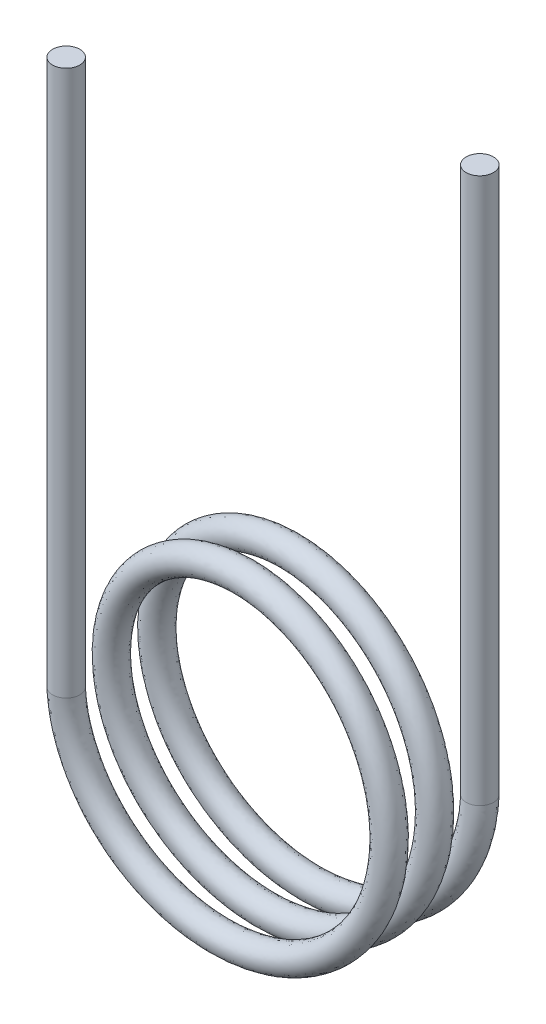
SolidWorks part; units mm, degrees
note: The reader was unsure of these and kept them because the rebuilt part matched: shared geometry of "Esboço2<2>".
ref_plane "Plano frontal" through (0, 0, 0) normal (0, 0, 1) x (1, 0, 0)
ref_plane "Plano superior" through (0, 0, 0) normal (0, 1, 0) x (1, 0, 0)
ref_plane "Plano direito" through (0, 0, 0) normal (1, 0, 0) x (0, 0, -1)
sketch "Esboço1" plane through (0, 0, 0) normal (0, 0, 1) x (1, 0, 0)
  circle A0 centre (0, 0) radius 24.75
  dimension "D1" = 49.5
curve "Hélice/Espiral2" pitch 7.5 height 18.75 turns 2.5
sketch "Esboço2" plane through (0, 0, 0) normal (0, 1, 0) x (1, 0, 0)
  circle A0 centre (24.75, 0) radius 2.25
  spline S0 degree 3 poles (24.75, 0) (24.75, -0.1133) (24.0725, -0.3411) (21.106, -0.6818) (16.4296, -1.0227) (10.4222, -1.3636) (3.5705, -1.7045) (-3.5705, -2.0455) (-10.4222, -2.3864) (-16.4296, -2.7273) (-21.106, -3.0682) (-24.0725, -3.4091) (-25.0888, -3.75) (-24.0725, -4.0909) (-21.106, -4.4318) (-16.4296, -4.7727) (-10.4222, -5.1136) (-3.5705, -5.4545) (3.5705, -5.7955) (10.4222, -6.1364) (16.4296, -6.4773) (21.106, -6.8182) (24.0725, -7.1591) (25.0888, -7.5) (24.0725, -7.8409) (21.106, -8.1818) (16.4296, -8.5227) (10.4222, -8.8636) (3.5705, -9.2045) (-3.5705, -9.5455) (-10.4222, -9.8864) (-16.4296, -10.2273) (-21.106, -10.5682) (-24.0725, -10.9091) (-25.0888, -11.25) (-24.0725, -11.5909) (-21.106, -11.9318) (-16.4296, -12.2727) (-10.4222, -12.6136) (-3.5705, -12.9545) (3.5705, -13.2955) (10.4222, -13.6364) (16.4296, -13.9773) (21.106, -14.3182) (24.0725, -14.6591) (25.0888, -15) (24.0725, -15.3409) (21.106, -15.6818) (16.4296, -16.0227) (10.4222, -16.3636) (3.5705, -16.7045) (-3.5705, -17.0455) (-10.4222, -17.3864) (-16.4296, -17.7273) (-21.106, -18.0682) (-24.0725, -18.4089) (-24.75, -18.6367) (-24.75, -18.75) knots 0 0 0 0 0.018182 0.036364 0.054545 0.072727 0.090909 0.109091 0.127273 0.145455 0.163636 0.181818 0.2 0.218182 0.236364 0.254545 0.272727 0.290909 0.309091 0.327273 0.345455 0.363636 0.381818 0.4 0.418182 0.436364 0.454545 0.472727 0.490909 0.509091 0.527273 0.545455 0.563636 0.581818 0.6 0.618182 0.636364 0.654545 0.672727 0.690909 0.709091 0.727273 0.745455 0.763636 0.781818 0.8 0.818182 0.836364 0.854545 0.872727 0.890909 0.909091 0.927273 0.945455 0.963636 0.981818 1 1 1 1 construction
  dimension "D1" = 4.5
sweep "Varredura1" add profiles "Esboço2" path "Hélice/Espiral2"
extrude "Ressalto-extrusão3" add sketch "Esboço2<2>" along normal blind 90
sketch "Esboço2<2>" plane through (0, 0, 0) normal (0, 1, 0) x (1, 0, 0) same geometry as "Esboço2"
ref_point "Ponto1"
sketch "Esboço3" plane through (0, 0, 0) normal (0, 1, 0) x (1, 0, 0)
  circle A0 centre (-24.75, -18.75) radius 2.25
  dimension "D1" = 4.5
extrude "Ressalto-extrusão8" add sketch "Esboço3" along normal blind 90
equation "\"diam_interno\"=45"
equation "\"diam_tubo\"=4.5"
equation "\"D1@Esboço2\"=\"diam_tubo\""
equation "\"turn_gap\"=3"
equation "\"turn_step\"=((\"diam_tubo\"/2)+(\"turn_gap\"/2))*2"
equation "\"coil_height\"=\"turn_step\"*2.5"
equation "\"D4@Hélice/Espiral2\"=\"turn_step\""
equation "\"D3@Hélice/Espiral2\"=\"coil_height\""
equation "\"D1@Esboço1\" = \"diam_interno\"+\"diam_tubo\""
equation "\"D1@Esboço3\"=\"diam_tubo\""
equation "\"coil_arm\"=90"
equation "\"D1@Ressalto-extrusão3\"=\"coil_arm\""
equation "\"D1@Ressalto-extrusão8\"=\"coil_arm\""
